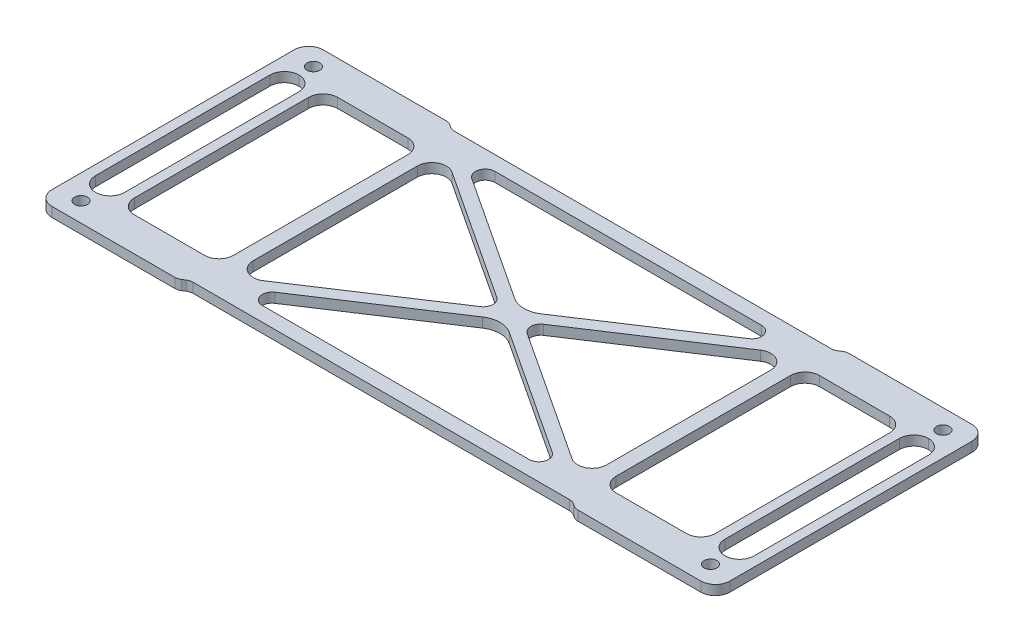
SolidWorks part; units mm, degrees
material "碳板"
ref_plane "前视基准面" through (0, 0, 0) normal (0, 0, 1) x (1, 0, 0)
ref_plane "上视基准面" through (0, 0, 0) normal (0, 1, 0) x (1, 0, 0)
ref_plane "右视基准面" through (0, 0, 0) normal (1, 0, 0) x (0, 0, -1)
sketch "草图1" plane through (0, 0, 0) normal (0, 1, 0) x (1, 0, 0)
  line L0 (-113.7082, 0) -> (103.7549, 0) construction
  line L1 (-65, 24) -> (65, 24) construction
  line L2 (-65, 24) -> (-65, -24) construction
  line L3 (-65, -24) -> (65, -24) construction
  line L4 (65, 24) -> (65, -24) construction
  line L5 (-65, 24) -> (65, -24) construction
  line L6 (-65, -24) -> (65, 24) construction
  line L7 (0, 62.0275) -> (0, -57.9828) construction
  line L13 (-70, 28) -> (70, 28)
  line L14 (-70, 28) -> (-70, -28)
  line L16 (-70, -28) -> (70, -28)
  line L17 (70, 28) -> (70, -28)
  line L18 (-70, 28) -> (70, -28) construction
  line L20 (-70, -28) -> (70, 28) construction
  circle A0 centre (-65, 24) radius 1.325
  circle A1 centre (65, 24) radius 1.325
  circle A2 centre (65, -24) radius 1.325
  circle A3 centre (-65, -24) radius 1.325
  point P0 (0, 0)
  point P13 (0, 0)
  point P15 (0, 0)
  dimension "D1" = 2.65
  dimension "D4" = 5
  dimension "D5" = 4
  dimension "D2" = 130
  dimension "D3" = 48
extrude "凸台-拉伸1" add sketch "草图1" along normal blind 2
sketch "草图3" plane through (0, 2, 0) normal (0, 1, 0) x (1, 0, 0)
  line L0 (-91.1364, 0) -> (83.5166, 0) construction
  line L1 (0, 46.1698) -> (0, -44.2648) construction
  line L2 (-39.5, 28) -> (-39.5, -28)
  line L3 (70, 28) -> (-70, 28) construction
  line L4 (-70, -28) -> (70, -28) construction
  line L5 (-35.8132, 25.0444) -> (37.1868, -22.9556)
  line L6 (-36.5, 24) -> (36.5, 24)
  line L7 (-36.5, 24) -> (-36.5, -24)
  line L8 (-36.5, -24) -> (36.5, -24)
  line L9 (36.5, 24) -> (36.5, -24)
  line L10 (-36.5, 24) -> (36.5, -24) construction
  line L11 (-36.5, -24) -> (36.5, 24) construction
  line L12 (-37.1868, -22.9556) -> (35.8132, 25.0444)
  line L13 (-37.1868, 22.9556) -> (35.8132, -25.0444)
  line L14 (-35.8132, -25.0444) -> (37.1868, 22.9556)
  line L15 (-70, 28) -> (-70, -28) construction
  line L20 (-60, 21) -> (-39.5, 21)
  line L21 (-60, 21) -> (-60, -21)
  line L22 (-60, -21) -> (-39.5, -21)
  line L23 (-39.5, 21) -> (-39.5, -21)
  line L24 (-60, 21) -> (-39.5, -21) construction
  line L25 (-60, -21) -> (-39.5, 21) construction
  line L26 (-68, 21) -> (-62, 21)
  line L27 (-68, 21) -> (-68, -21)
  line L28 (-68, -21) -> (-62, -21)
  line L29 (-62, 21) -> (-62, -21)
  line L30 (-68, 21) -> (-62, -21) construction
  line L31 (-68, -21) -> (-62, 21) construction
  line L32 (60, -21) -> (39.5, -21)
  line L33 (39.5, 21) -> (39.5, -21)
  line L34 (60, 21) -> (39.5, 21)
  line L35 (60, 21) -> (60, -21)
  line L36 (68, -21) -> (62, -21)
  line L37 (62, 21) -> (62, -21)
  line L38 (68, 21) -> (62, 21)
  line L39 (68, 21) -> (68, -21)
  circle A0 centre (-65, 24) radius 1.325 construction
  point P11 (0, 0)
  point P24 (-49.75, 0)
  point P32 (-65, 0)
  dimension "D1" = 79
  dimension "D2" = 3
  dimension "D3" = 4
  dimension "D6" = 5
  dimension "D7" = 3
  dimension "D8" = 2
  dimension "D9" = 2
  dimension "D4" = 1.25
  dimension "D5" = 1.25
extrude "切除-拉伸1" cut sketch "草图3" against normal blind 10 contours L21 L22 L2 L20 | L29 L26 L27 L28 | L13 L7 L12 | L5 L12 L6 | L14 L5 L9 | L14 L8 L13 | L35 L34 L33 L32 | L39 L38 L37 L36 region at (-49.75, 2, 0) region at (0, 2, -16.4987) region at (25.0917, 2, 0) region at (-25.0917, 2, 0) region at (0, 2, 16.4987) region at (-65, 2, 0) region at (49.75, 2, 0) region at (65, 2, 0)
fillet "圆角1" radius 3 20 edges at (-70, 1, 28) (-70, 1, -28) (70, 1, -28) (70, 1, 28) (68, 1, 21) (62, 1, 21) (62, 1, -21) (68, 1, -21) (60, 1, 21) (39.5, 1, 21) (39.5, 1, -21) (60, 1, -21) (-62, 1, 21) (-68, 1, 21) (-68, 1, -21) (-62, 1, -21) (-39.5, 1, 21) (-60, 1, 21) (-60, 1, -21) (-39.5, 1, -21)
fillet "圆角2" radius 2 6 edges at (-34.2248, 1, -24) (34.2248, 1, -24) (34.2248, 1, 24) (-34.2248, 1, 24) (2.2752, 1, 0) (-2.2752, 1, 0)
fillet "圆角3" radius 3 4 edges at (36.5, 1, 22.504) (36.5, 1, -22.504) (-36.5, 1, 22.504) (-36.5, 1, -22.504)
fillet "圆角4" radius 5 2 edges at (0, 1, -1.496) (0, 1, 1.496)
sketch "草图4" plane through (0, 2, 0) normal (0, 1, 0) x (1, 0, 0)
  line L0 (0, 28) -> (0, -28) construction
  line L1 (67, 28) -> (-67, 28) construction
  line L2 (-67, -28) -> (67, -28) construction
  line L3 (-41.0208, 28) -> (-39.5, 27)
  line L4 (-39.5, 27) -> (39.5, 27)
  line L5 (-70, 0) -> (70, 0) construction
  line L6 (-70, 25) -> (-70, -25) construction
  line L7 (70, -25) -> (70, 25) construction
  line L8 (-28.6417, 20.3289) -> (-2.747, 3.3023) construction
  line L9 (41.0208, 28) -> (39.5, 27)
  line L10 (41.0208, -28) -> (39.5, -27)
  line L11 (-41.0208, -28) -> (-39.5, -27)
  line L12 (-39.5, -27) -> (39.5, -27)
  line L13 (-41.0208, 28) -> (41.0208, 28)
  line L14 (-41.0208, -28) -> (41.0208, -28)
  point P20 (0, 27)
  dimension "D1" = 79
  dimension "D2" = 54
extrude "切除-拉伸2" cut sketch "草图4" against normal through all
fillet "圆角5" radius 2 8 edges at (-41.0208, 1, 28) (-39.5, 1, 27) (39.5, 1, 27) (41.0208, 1, 28) (41.0208, 1, -28) (39.5, 1, -27) (-39.5, 1, -27) (-41.0208, 1, -28)
